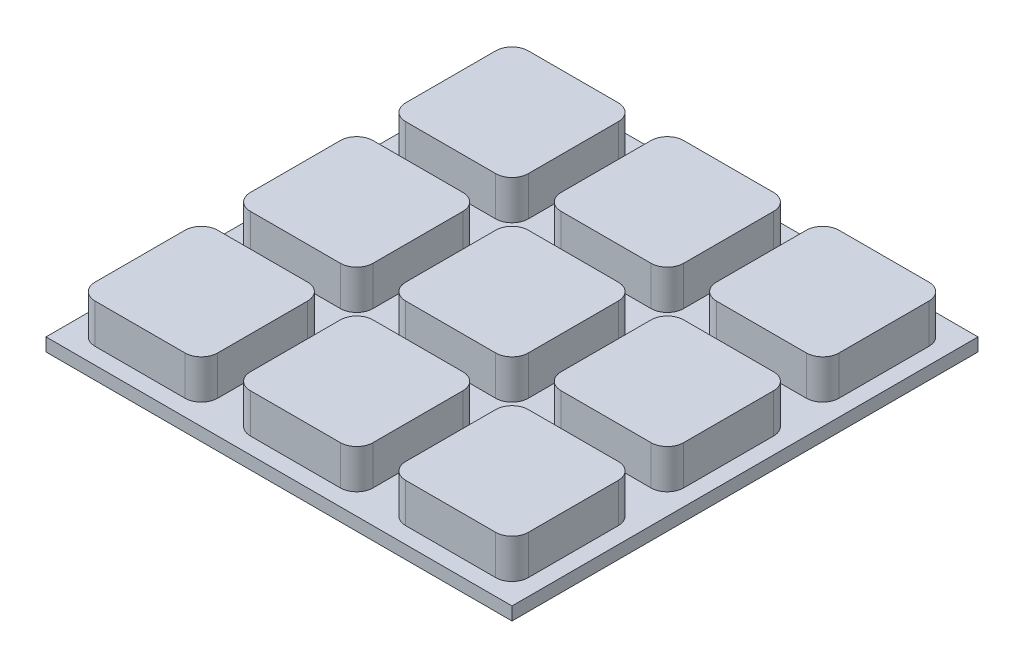
SolidWorks part; units mm, degrees
ref_plane "Front Plane" through (0, 0, 0) normal (0, 0, 1) x (1, 0, 0)
ref_plane "Top Plane" through (0, 0, 0) normal (0, 1, 0) x (1, 0, 0)
ref_plane "Right Plane" through (0, 0, 0) normal (1, 0, 0) x (0, 0, -1)
sketch "Sketch1" plane through (0, 0, 0) normal (0, 1, 0) x (1, 0, 0)
  line L1 (30.5, -30.5) -> (-30.5, -30.5)
  line L2 (30.5, -30.5) -> (30.5, 30.5)
  line L3 (30.5, 30.5) -> (-30.5, 30.5)
  line L4 (-30.5, -30.5) -> (-30.5, 30.5)
  line L5 (30.5, -30.5) -> (-30.5, 30.5) construction
  line L6 (30.5, 30.5) -> (-30.5, -30.5) construction
  point P0 (0, 0)
  dimension "D1" = 61
  dimension "D2" = 61
extrude "Boss-Extrude1" add sketch "Sketch1" along normal blind 1.6
sketch "Sketch2" plane through (0, 1.6, 0) normal (0, 1, 0) x (1, 0, 0)
  line L1 (-26.5, 26.5) -> (-11.5, 26.5)
  line L2 (-26.5, 26.5) -> (-26.5, 11.5)
  line L3 (-26.5, 11.5) -> (-11.5, 11.5)
  line L4 (-11.5, 26.5) -> (-11.5, 11.5)
  line L5 (-26.5, 26.5) -> (-11.5, 11.5) construction
  line L6 (-26.5, 11.5) -> (-11.5, 26.5) construction
  line L7 (-7.5, 26.5) -> (7.5, 26.5)
  line L8 (-7.5, 26.5) -> (-7.5, 11.5)
  line L9 (-7.5, 11.5) -> (7.5, 11.5)
  line L10 (7.5, 26.5) -> (7.5, 11.5)
  line L11 (-7.5, 26.5) -> (7.5, 11.5) construction
  line L12 (-7.5, 11.5) -> (7.5, 26.5) construction
  line L13 (11.5, 26.5) -> (26.5, 26.5)
  line L14 (11.5, 26.5) -> (11.5, 11.5)
  line L15 (11.5, 11.5) -> (26.5, 11.5)
  line L16 (26.5, 26.5) -> (26.5, 11.5)
  line L17 (11.5, 26.5) -> (26.5, 11.5) construction
  line L18 (11.5, 11.5) -> (26.5, 26.5) construction
  line L19 (11.5, 7.5) -> (26.5, 7.5)
  line L20 (11.5, 7.5) -> (11.5, -7.5)
  line L21 (11.5, -7.5) -> (26.5, -7.5)
  line L22 (26.5, 7.5) -> (26.5, -7.5)
  line L23 (11.5, 7.5) -> (26.5, -7.5) construction
  line L24 (11.5, -7.5) -> (26.5, 7.5) construction
  line L25 (-7.5, 7.5) -> (7.5, 7.5)
  line L26 (-7.5, 7.5) -> (-7.5, -7.5)
  line L27 (-7.5, -7.5) -> (7.5, -7.5)
  line L28 (7.5, 7.5) -> (7.5, -7.5)
  line L29 (-7.5, 7.5) -> (7.5, -7.5) construction
  line L30 (-7.5, -7.5) -> (7.5, 7.5) construction
  line L31 (-26.5, 7.5) -> (-11.5, 7.5)
  line L32 (-26.5, 7.5) -> (-26.5, -7.5)
  line L33 (-26.5, -7.5) -> (-11.5, -7.5)
  line L34 (-11.5, 7.5) -> (-11.5, -7.5)
  line L35 (-26.5, 7.5) -> (-11.5, -7.5) construction
  line L36 (-26.5, -7.5) -> (-11.5, 7.5) construction
  line L37 (-26.5, -11.5) -> (-11.5, -11.5)
  line L38 (-26.5, -11.5) -> (-26.5, -26.5)
  line L39 (-26.5, -26.5) -> (-11.5, -26.5)
  line L40 (-11.5, -11.5) -> (-11.5, -26.5)
  line L41 (-26.5, -11.5) -> (-11.5, -26.5) construction
  line L42 (-26.5, -26.5) -> (-11.5, -11.5) construction
  line L43 (-7.5, -11.5) -> (7.5, -11.5)
  line L44 (-7.5, -11.5) -> (-7.5, -26.5)
  line L45 (-7.5, -26.5) -> (7.5, -26.5)
  line L46 (7.5, -11.5) -> (7.5, -26.5)
  line L47 (-7.5, -11.5) -> (7.5, -26.5) construction
  line L48 (-7.5, -26.5) -> (7.5, -11.5) construction
  line L49 (11.5, -11.5) -> (26.5, -11.5)
  line L50 (11.5, -11.5) -> (11.5, -26.5)
  line L51 (11.5, -26.5) -> (26.5, -26.5)
  line L52 (26.5, -11.5) -> (26.5, -26.5)
  line L53 (11.5, -11.5) -> (26.5, -26.5) construction
  line L54 (11.5, -26.5) -> (26.5, -11.5) construction
  point P0 (-19, 19)
  point P5 (0, 19)
  point P10 (19, 19)
  point P15 (19, 0)
  point P20 (0, 0)
  point P25 (-19, 0)
  point P30 (-19, -19)
  point P35 (0, -19)
  point P40 (19, -19)
  dimension "D1" = 15
  dimension "D2" = 4
  dimension "D3" = 4
  dimension "D4" = 4
  dimension "D5" = 4
extrude "Boss-Extrude2" add sketch "Sketch2" along normal blind 4.8
fillet "Fillet1" radius 2 36 edges at (26.5, 4, -11.5) (26.5, 4, -26.5) (11.5, 4, -26.5) (11.5, 4, -11.5) (-7.5, 4, -11.5) (7.5, 4, -11.5) (7.5, 4, -26.5) (-7.5, 4, -26.5) (-26.5, 4, -26.5) (-11.5, 4, -26.5) (-11.5, 4, -11.5) (-26.5, 4, -11.5) (-11.5, 4, 11.5) (-11.5, 4, 26.5) (-26.5, 4, 26.5) (-26.5, 4, 11.5) (-7.5, 4, 11.5) (-7.5, 4, 26.5) (7.5, 4, 11.5) (7.5, 4, 26.5) (26.5, 4, 26.5) (11.5, 4, 26.5) (11.5, 4, 11.5) (26.5, 4, 11.5) (11.5, 4, -7.5) (26.5, 4, -7.5) (26.5, 4, 7.5) (11.5, 4, 7.5) (7.5, 4, 7.5) (7.5, 4, -7.5) (-7.5, 4, 7.5) (-7.5, 4, -7.5) (-26.5, 4, -7.5) (-11.5, 4, -7.5) (-11.5, 4, 7.5) (-26.5, 4, 7.5)
sketch "Sketch4" plane through (0, 0, 0) normal (0, -1, 0) x (1, 0, 0)
  line L1 (28.5, -28.5) -> (-28.5, -28.5)
  line L2 (28.5, -28.5) -> (28.5, 28.5)
  line L3 (28.5, 28.5) -> (-28.5, 28.5)
  line L4 (-28.5, -28.5) -> (-28.5, 28.5)
  line L5 (28.5, -28.5) -> (-28.5, 28.5) construction
  line L6 (28.5, 28.5) -> (-28.5, -28.5) construction
  point P0 (0, 0)
  dimension "D1" = 57
extrude "Cut-Extrude1" cut sketch "Sketch4" against normal up to next (6.4 mm away) flip side to cut
